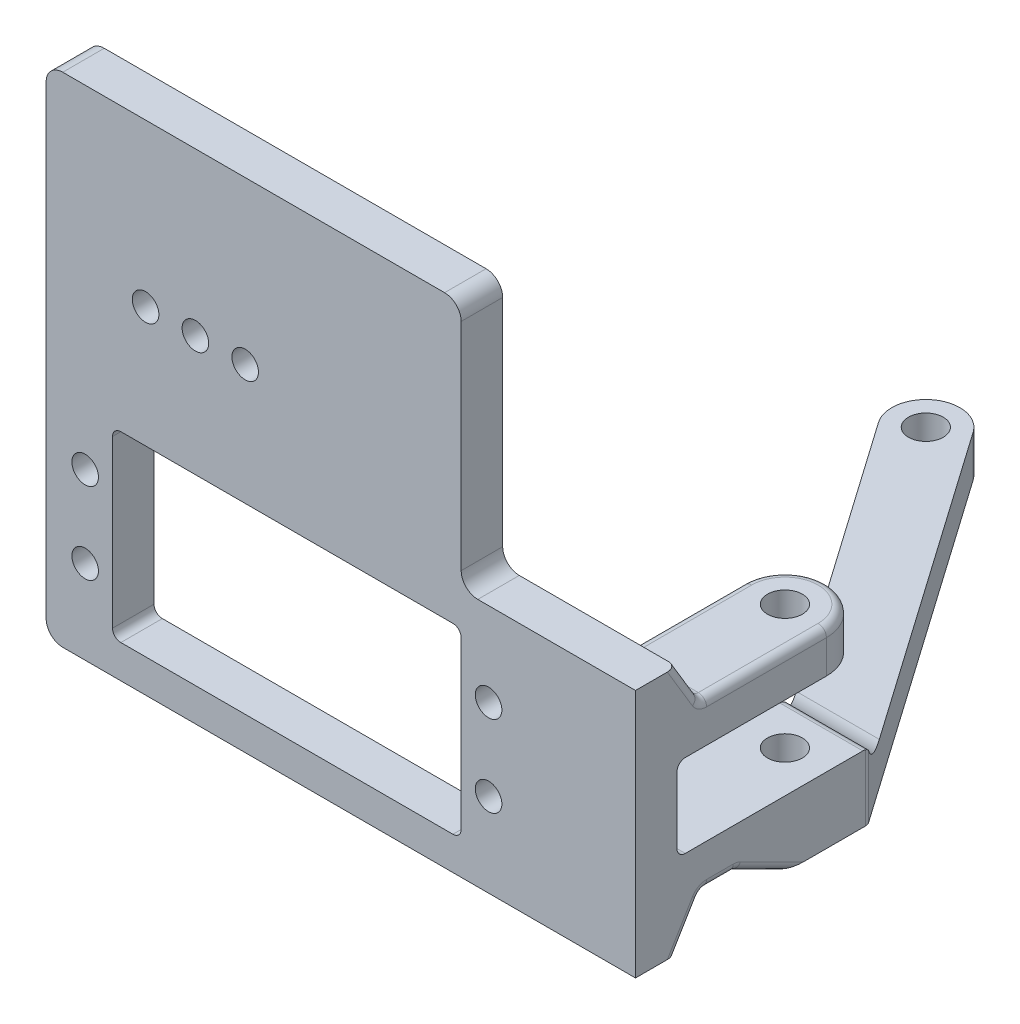
SolidWorks part; units mm, degrees
ref_plane "前视基准面" through (0, 0, 0) normal (0, 0, 1) x (1, 0, 0)
ref_plane "上视基准面" through (0, 0, 0) normal (0, 1, 0) x (1, 0, 0)
ref_plane "右视基准面" through (0, 0, 0) normal (1, 0, 0) x (0, 0, -1)
other "Configuration Table"
sketch "草图1" plane through (0, 0, 0) normal (0, 0, 1) x (1, 0, 0)
  line L1 (0, 0) -> (65, 0)
  line L2 (0, 0) -> (0, 30)
  line L3 (0, 30) -> (65, 30)
  line L4 (65, 0) -> (65, 30)
  dimension "D1" = 65
  dimension "D2" = 30
extrude "凸台-拉伸1" add sketch "草图1" along normal blind 5
sketch "草图2" plane through (0, 0, 5) normal (0, 0, 1) x (1, 0, 0)
  line L1 (8, 26) -> (50, 26)
  line L2 (8, 26) -> (8, 4)
  line L3 (8, 4) -> (50, 4)
  line L4 (50, 26) -> (50, 4)
  line L6 (65, 30) -> (0, 30) construction
  line L8 (0, 30) -> (0, 0) construction
  dimension "D1" = 42
  dimension "D2" = 22
  dimension "D3" = 4
  dimension "D4" = 8
extrude "切除-拉伸1" cut sketch "草图2" against normal blind 5
sketch "草图3" plane through (0, 0, 5) normal (0, 0, 1) x (1, 0, 0)
  line L0 (0, 15) -> (65, 15) construction
  line L1 (0, 30) -> (0, 0) construction
  line L2 (65, 0) -> (65, 30) construction
  line L3 (8, 26) -> (8, 4) construction
  line L4 (50, 4) -> (50, 26) construction
  circle A0 centre (4.7, 19.9) radius 1.6
  circle A2 centre (53.3, 19.9) radius 1.6
  circle A3 centre (53.3, 10.1) radius 1.6
  circle A4 centre (4.7, 10.1) radius 1.6
  dimension "D1" = 3.2
  dimension "D3" = 3.2
  dimension "D5" = 9.8
  dimension "D6" = 9.8
  dimension "D2" = 3.3
  dimension "D4" = 3.3
extrude "切除-拉伸2" cut sketch "草图3" against normal blind 5
fillet "圆角1" radius 1 4 edges at (50, 26, 2.5) (50, 4, 2.5) (8, 4, 2.5) (8, 26, 2.5)
sketch "草图4" plane through (0, 0, 5) normal (0, 0, 1) x (1, 0, 0)
  line L1 (65, 30) -> (83, 30)
  line L2 (65, 30) -> (65, 0)
  line L3 (65, 0) -> (83, 0)
  line L4 (83, 30) -> (83, 0)
  dimension "D1" = 18
extrude "凸台-拉伸2" add sketch "草图4" against normal blind 5
sketch "草图6" plane through (0, 0, 0) normal (0, 0, -1) x (-1, 0, 0)
  line L0 (-61, 5) -> (-61, 10)
  line L1 (-83, 0) -> (-83, 30) construction
  line L2 (-50, 15) -> (-83, 15) construction
  line L3 (-50, 5) -> (-50, 25) construction
  line L4 (-71, 25) -> (-61, 25)
  line L5 (-71, 25) -> (-71, 20)
  line L6 (-71, 20) -> (-61, 20)
  line L7 (-61, 25) -> (-61, 20)
  line L12 (-71, 10) -> (-61, 10)
  line L13 (-71, 5) -> (-71, 10)
  line L14 (-71, 5) -> (-61, 5)
  dimension "D1" = 10
  dimension "D2" = 5
  dimension "D3" = 12
  dimension "D4" = 5
extrude "凸台-拉伸4" add sketch "草图6" along normal blind 23
fillet "圆角3" 2 edges at (61, 22.5, -23) (71, 22.5, -23) type full round first side face at (61, 22.5, -11.5) second side face at (71, 22.5, -11.5) middle face at (66, 22.5, -23)
sketch "草图8" plane through (0, 0, 0) normal (0, 0, -1) x (-1, 0, 0)
  line L0 (0, 0) -> (-83, 0) construction
  line L1 (-83, 30) -> (-71, 30)
  line L2 (-83, 30) -> (-83, 0)
  line L3 (-83, 0) -> (-71, 0)
  line L4 (-71, 30) -> (-71, 0)
  line L5 (-71, 10) -> (-71, 5) construction
extrude "切除-拉伸4" cut sketch "草图8" against normal through all
sketch "草图9" plane through (71, 0, 0) normal (1, 0, 0) x (0, 0, -1)
  line L8 (0, 30) -> (0, 25)
  line L9 (0, 25) -> (3, 25)
  line L10 (18, 25) -> (0, 25) construction
  line L11 (3, 25) -> (0, 30)
  line L12 (0, 0) -> (0, 5)
  line L13 (0, 5) -> (3, 5)
  line L14 (23, 5) -> (0, 5) construction
  line L15 (3, 5) -> (0, 0)
  dimension "D1" = 3
  dimension "D2" = 3
extrude "凸台-拉伸5" add sketch "草图9" against normal blind 10
sketch "草图10" plane through (0, 25, 0) normal (0, 1, 0) x (1, 0, 0)
  circle A0 centre (66, 18) radius 2.1
  dimension "D1" = 4.2
extrude "切除-拉伸5" cut sketch "草图10" against normal through all
sketch "草图11" plane through (0, 5, 0) normal (0, -1, 0) x (1, 0, 0)
  line L0 (61, -23) -> (61, -3) construction
  line L1 (61, -13) -> (71, -13)
  line L2 (61, -13) -> (61, -23)
  line L3 (61, -23) -> (71, -23)
  line L4 (71, -13) -> (71, -23)
extrude "凸台-拉伸6" add sketch "草图11" along normal blind 3
sketch "草图12" plane through (0, 2, 0) normal (0, -1, 0) x (-1, 0, 0)
  line L0 (-61, 13) -> (-71, 23) construction
  circle A0 centre (-66, 18) radius 2.1
  dimension "D1" = 4.2
extrude "切除-拉伸6" cut sketch "草图12" against normal through all
sketch "草图13" plane through (71, 0, 0) normal (1, 0, 0) x (0, 0, -1)
  line L0 (7, 5) -> (13, 2)
  line L1 (13, 5) -> (3, 5) construction
  line L2 (13, 2) -> (13, 5)
  line L3 (13, 5) -> (7, 5)
  dimension "D1" = 6
extrude "凸台-拉伸7" add sketch "草图13" against normal blind 10
sketch "草图14" plane through (0, 2, 0) normal (0, -1, 0) x (-1, 0, 0)
  line L6 (-71, 23) -> (-39.0313, 68.6561)
  line L7 (-39.0313, 68.6561) -> (-32.3212, 63.9576)
  line L8 (-32.3212, 63.9576) -> (-61, 23)
  line L9 (-71, 23) -> (-61, 23)
  line L10 (-61, 13) -> (-61, 23) construction
  dimension "D1" = 50
  dimension "D2" = 145
extrude "凸台-拉伸8" add sketch "草图14" against normal blind 5
fillet "圆角6" 2 edges at (39.0313, 4.5, -68.6561) (32.3212, 4.5, -63.9576) type full round first side face at (55.0156, 4.5, -45.828) second side face at (46.6606, 4.5, -43.4788) middle face at (35.6762, 4.5, -66.3068)
sketch "草图15" plane through (0, 2, 0) normal (0, -1, 0) x (-1, 0, 0)
  circle A0 centre (-38.0255, 62.9518) radius 2.1
  dimension "D1" = 4.2
extrude "切除-拉伸9" cut sketch "草图15" against normal blind 5
fillet "圆角7" radius 5 1 edges at (66, 7, -23)
fillet "圆角8" radius 1 19 edges at (71, 27.5, -1.5) (71, 25, -10.5) (66, 25, -23) (61, 3.5, -10) (71, 3.5, -10) (61, 25, -10.5) (61, 5, -5) (71, 5, -5) (61, 27.5, -1.5) (66, 25, -3) (66, 20, 0) (66, 10, 0) (61, 2.5, -1.5) (71, 2.5, -1.5) (66, 10, -23) (71, 6, -23) (66, 2, -13) (66, 5, -7) (66, 5, -3)
fillet "圆角9" radius 1 1 edges at (61, 5.8948, -23)
sketch "草图20" plane through (0, 0, 0) normal (0, 0, -1) x (-1, 0, 0)
  line L0 (-50, 5) -> (-50, 25) construction
  line L1 (0, 30) -> (-50, 30)
  line L2 (0, 30) -> (0, 60)
  line L3 (0, 60) -> (-50, 60)
  line L4 (-50, 30) -> (-50, 60)
  dimension "D1" = 30
extrude "凸台-拉伸12" add sketch "草图20" against normal blind 5
sketch "草图21" plane through (0, 0, 5) normal (0, 0, 1) x (1, 0, 0)
  line L0 (0, 60) -> (0, 0) construction
  line L1 (0, 60) -> (50, 60) construction
  circle A0 centre (17.98, 40.5) radius 1.6
  dimension "D1" = 3.2
  dimension "D3" = 19.5
  dimension "D2" = 17.98
extrude "切除-拉伸11" cut sketch "草图21" against normal blind 5
fillet "圆角10" radius 2 4 edges at (0, 0, 2.5) (0, 60, 2.5) (50, 60, 2.5) (50, 30, 2.5)
sketch "草图22" plane through (0, 0, 5) normal (0, 0, 1) x (1, 0, 0)
  line L0 (0, 40.5) -> (50, 40.5) construction
  line L1 (50, 58) -> (50, 32) construction
  line L2 (0, 58) -> (0, 2) construction
  circle A0 centre (17.98, 40.5) radius 1.6 construction
  circle A1 centre (17.98, 40.5) radius 1.6 construction
  circle A2 centre (23.98, 40.5) radius 1.6
  circle A3 centre (11.98, 40.5) radius 1.6
  dimension "D1" = 3.2
  dimension "D2" = 3.2
  dimension "D3" = 6
  dimension "D4" = 6
extrude "切除-拉伸12" cut sketch "草图22" against normal blind 5
